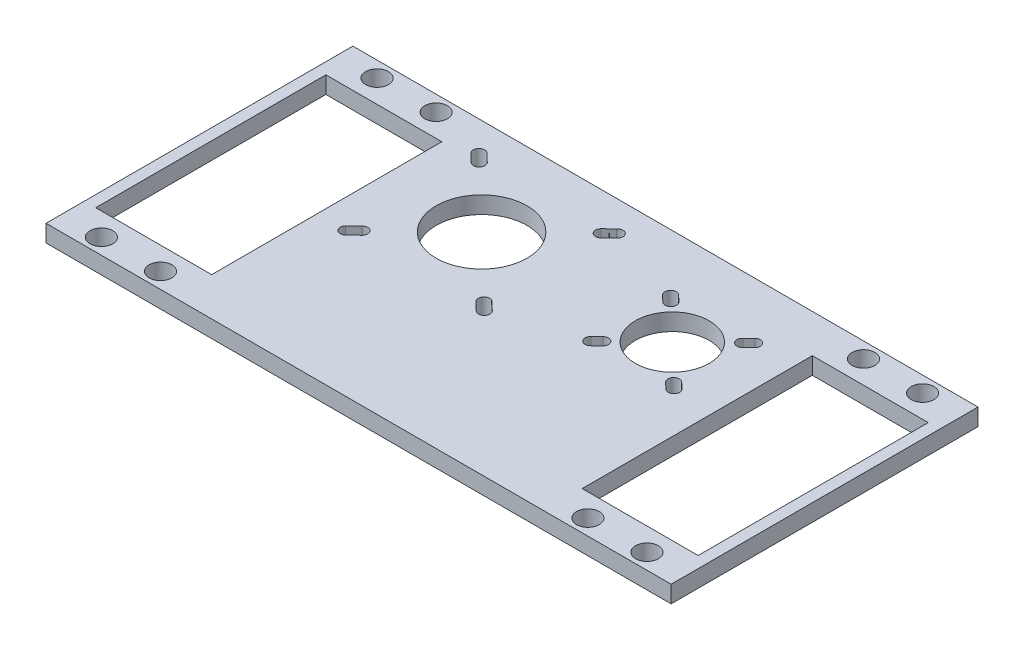
SolidWorks part; units mm, degrees
ref_plane "Plan de face" through (0, 0, 0) normal (0, 0, 1) x (1, 0, 0)
ref_plane "Plan de dessus" through (0, 0, 0) normal (0, 1, 0) x (1, 0, 0)
ref_plane "Plan de droite" through (0, 0, 0) normal (1, 0, 0) x (0, 0, -1)
sketch "Esquisse1" plane through (0, 0, 0) normal (0, 1, 0) x (1, 0, 0)
  line L1 (-54, 35.0217) -> (56, 35.0217)
  line L2 (-54, 35.0217) -> (-54, -18.9783)
  line L3 (-54, -18.9783) -> (56, -18.9783)
  line L4 (56, 35.0217) -> (56, -18.9783)
  dimension "D1" = 54
  dimension "D2" = 110
extrude "Boss.-Extru.1" add sketch "Esquisse1" along normal blind 3
sketch "Esquisse2" plane through (0, 3, 0) normal (0, 1, 0) x (1, 0, 0)
  line L0 (56, 35.0217) -> (-54, 35.0217) construction
  line L1 (-52, 28.2717) -> (-31.6, 28.2717)
  line L2 (-52, 28.2717) -> (-52, -12.2283)
  line L3 (-52, -12.2283) -> (-31.6, -12.2283)
  line L4 (-31.6, 28.2717) -> (-31.6, -12.2283)
  line L6 (-54, 35.0217) -> (-54, -18.9783) construction
  line L7 (33.6, 28.2717) -> (54, 28.2717)
  line L8 (33.6, 28.2717) -> (33.6, -12.2283)
  line L9 (33.6, -12.2283) -> (54, -12.2283)
  line L10 (54, 28.2717) -> (54, -12.2283)
  line L11 (56, -18.9783) -> (56, 35.0217) construction
  circle A0 centre (-47, 32.2717) radius 2
  circle A1 centre (-36.6, 32.2717) radius 2
  circle A2 centre (-47, -16.2283) radius 2
  circle A3 centre (-36.6, -16.2283) radius 2
  circle A4 centre (38.6, 32.2717) radius 2
  circle A5 centre (49, 32.2717) radius 2
  circle A6 centre (38.6, -16.2283) radius 2
  circle A7 centre (49, -16.2283) radius 2
  dimension "D7" = 4
  dimension "D8" = 4
  dimension "D9" = 4
  dimension "D10" = 4
  dimension "D21" = 4
  dimension "D22" = 4
  dimension "D23" = 4
  dimension "D24" = 4
  dimension "D1" = 40.5
  dimension "D2" = 20.4
  dimension "D3" = 6.75
  dimension "D4" = 2
  dimension "D5" = 4
  dimension "D6" = 4
  dimension "D11" = 4
  dimension "D12" = 4
  dimension "D13" = 5
  dimension "D14" = 5
  dimension "D15" = 5
  dimension "D16" = 5
  dimension "D17" = 40.5
  dimension "D18" = 20.4
  dimension "D19" = 4
  dimension "D20" = 4
  dimension "D25" = 4
  dimension "D26" = 4
  dimension "D27" = 5
  dimension "D28" = 5
  dimension "D29" = 5
  dimension "D30" = 5
  dimension "D31" = 2
  dimension "D32" = 6.75
extrude "Enlèv. mat.-Extru.1" cut sketch "Esquisse2" against normal blind 46
sketch "Esquisse3" plane through (0, 3, 0) normal (0, 1, 0) x (1, 0, 0)
  line L0 (-4.2842, 6.9571) -> (-2.7941, 5.5204)
  line L5 (26.6, 25.1266) -> (25.518, 24.0877) construction
  line L6 (-41.8001, 18.0218) -> (43.7999, 18.0218) construction
  line L7 (27.2926, 24.4052) -> (26.2105, 23.3664)
  line L8 (-4.3393, 29.0362) -> (-2.9466, 30.3684)
  line L9 (-2.9466, 29.0852) -> (-2.9466, 29.0788)
  line L10 (-2.9466, 27.6021) -> (-1.4865, 29.0059)
  line L11 (33.6, 28.2717) -> (33.6, -12.2283) construction
  line L12 (-25.9157, 5.5204) -> (-24.3881, 6.9802)
  line L13 (-1.4068, 6.9611) -> (-2.8532, 8.3521)
  line L14 (-2.1, 6.2403) -> (-1.3792, 5.5471)
  line L15 (-25.7698, 6.9802) -> (-25.7722, 6.9802)
  line L16 (-27.2687, 6.9802) -> (-25.7698, 8.4262)
  line L17 (9.8, 27.0468) -> (28.6, 8.9968)
  line L18 (-27.2932, 29.0825) -> (-25.8517, 27.6962)
  line L19 (-25.8869, 29.1021) -> (-25.8873, 29.1178)
  line L20 (-25.9229, 30.5392) -> (-24.4654, 29.1378)
  line L21 (9.8, 27.0468) -> (28.6, 27.0468)
  line L22 (-25.8873, 29.1178) -> (-25.8792, 29.1101)
  line L23 (9.8, 27.0468) -> (9.8, 8.9968)
  line L24 (9.8, 8.9968) -> (28.6, 8.9968)
  line L25 (28.6, 27.0468) -> (28.6, 8.9968)
  line L26 (9.8, 8.9968) -> (28.6, 27.0468)
  line L27 (25.9074, 25.8479) -> (24.8254, 24.8091)
  line L28 (26.5169, 10.9968) -> (25.4349, 12.0357) construction
  line L29 (25.8243, 10.2755) -> (24.7423, 11.3143)
  line L30 (27.2095, 11.7182) -> (26.1274, 12.757)
  line L31 (11.8831, 10.9968) -> (12.9651, 12.0357) construction
  line L32 (11.1905, 11.7182) -> (12.2726, 12.757)
  line L33 (12.5757, 10.2755) -> (13.6577, 11.3143)
  line L34 (11.8831, 25.0468) -> (12.9651, 24.0079) construction
  line L35 (12.5757, 25.7682) -> (13.6577, 24.7293)
  line L36 (11.1905, 24.3255) -> (12.2726, 23.2866)
  circle A0 centre (-14.35, 18.0218) radius 8
  arc A1 (-2.7941, 5.5204) -> (-1.4068, 6.9611) centre (-2.1, 6.2403) ccw
  arc A2 (-2.9466, 29.0852) -> (-2.9003, 29.0336) centre (-2.1795, 29.7268) ccw
  arc A3 (-27.1565, 7.0884) -> (-25.7523, 5.6765) centre (-26.5205, 6.3168) ccw
  arc A4 (-25.8869, 29.1022) -> (-25.8792, 29.1101) centre (-26.6, 29.8033) ccw
  arc A5 (-25.8517, 27.6962) -> (-24.4654, 29.1378) centre (-25.1585, 28.4169) ccw
  arc A7 (-4.2842, 29.0889) -> (-2.9098, 27.6375) centre (-3.621, 28.3404) ccw
  arc A8 (-2.8435, 8.3428) -> (-4.1835, 6.86) centre (-3.5415, 7.6267) ccw
  arc A9 (-1.4865, 29.0059) -> (-2.9466, 30.3684) centre (-2.1795, 29.7268) ccw
  arc A10 (-2.9003, 29.0336) -> (-2.9466, 29.0788) centre (-3.621, 28.3404) ccw
  arc A11 (-24.3881, 6.9802) -> (-25.7766, 8.4196) centre (-25.079, 7.7032) ccw
  arc A12 (-25.8792, 29.1101) -> (-25.8869, 29.1021) centre (-25.1585, 28.4169) ccw
  arc A13 (-25.8912, 30.5087) -> (-27.2932, 29.0825) centre (-26.6, 29.8033) ccw
  circle A14 centre (19.2, 18.0218) radius 6.5
  arc A15 (27.2926, 24.4052) -> (25.9074, 25.8479) centre (26.6, 25.1266) ccw
  arc A16 (24.8254, 24.8091) -> (26.2105, 23.3664) centre (25.518, 24.0877) ccw
  arc A17 (25.8243, 10.2755) -> (27.2095, 11.7182) centre (26.5169, 10.9968) ccw
  arc A18 (26.1274, 12.757) -> (24.7423, 11.3143) centre (25.4349, 12.0357) ccw
  arc A19 (11.1905, 11.7182) -> (12.5757, 10.2755) centre (11.8831, 10.9968) ccw
  arc A20 (13.6577, 11.3143) -> (12.2726, 12.757) centre (12.9651, 12.0357) ccw
  arc A21 (12.5757, 25.7682) -> (11.1905, 24.3255) centre (11.8831, 25.0468) ccw
  arc A22 (12.2726, 23.2866) -> (13.6577, 24.7293) centre (12.9651, 24.0079) ccw
  point P6 (26.059, 24.6072)
  point P63 (25.9759, 11.5162)
  point P70 (12.4241, 11.5162)
  point P75 (12.4241, 24.5274)
  point P82 (0, 0)
  point P85 (0, 0)
  point P86 (0, 0)
  dimension "D5" = 16
  dimension "D10" = 2
  dimension "D11" = 2
  dimension "D12" = 2
  dimension "D13" = 2
  dimension "D14" = 1
  dimension "D15" = 2
  dimension "D16" = 2
  dimension "D17" = 2
  dimension "D18" = 2
  dimension "D2" = 13
  dimension "D3" = 14.4
  dimension "D7" = 1
  dimension "D20" = 1
  dimension "D21" = 1
  dimension "D4" = 18.8
  dimension "D6" = 18.05
  dimension "D8" = 1.5
  dimension "D9" = 2
  dimension "D19" = 1.5
  dimension "D22" = 1.5
  dimension "D23" = 1.5
  dimension "D24" = 2
  dimension "D25" = 2
extrude "Enlèv. mat.-Extru.2" cut sketch "Esquisse3" against normal blind 10 contours L10 A9 L8 A7 A2 A10 L9 | A0 | L20 A13 L18 A5 L22 A12 L19 | L12 A11 L16 A3 | L13 A8 L0 A1 region at (-2.8204, 3, -6.9337) region at (-2.8998, 3, -29.0329) region at (-25.7997, 3, -7.0107) region at (-25.8793, 3, -29.1101) region at (-14.35, 3, -18.0218)
extrude "Enlèv. mat.-Extru.3" cut sketch "Esquisse3<3>" against normal blind 15 contours L17 A22 L35 A21 | L36 A22 L17 A21 | L27 A16 L26 A15 | L26 A16 L7 A15 | L26 A20 L32 A19 | L33 A20 L26 A19 | L30 A18 L17 A17 | L17 A18 L29 A17 | A14 region at (26.3785, 3, -24.2744) region at (25.7395, 3, -24.9399) region at (12.7436, 3, -24.8602) region at (12.1046, 3, -24.1946) region at (25.6564, 3, -11.1835) region at (26.2954, 3, -11.849) region at (12.1046, 3, -11.849) region at (12.7436, 3, -11.1835)
sketch "Esquisse3<3>" plane through (0, 3, 0) normal (0, 1, 0) x (1, 0, 0) same geometry as "Esquisse3"
